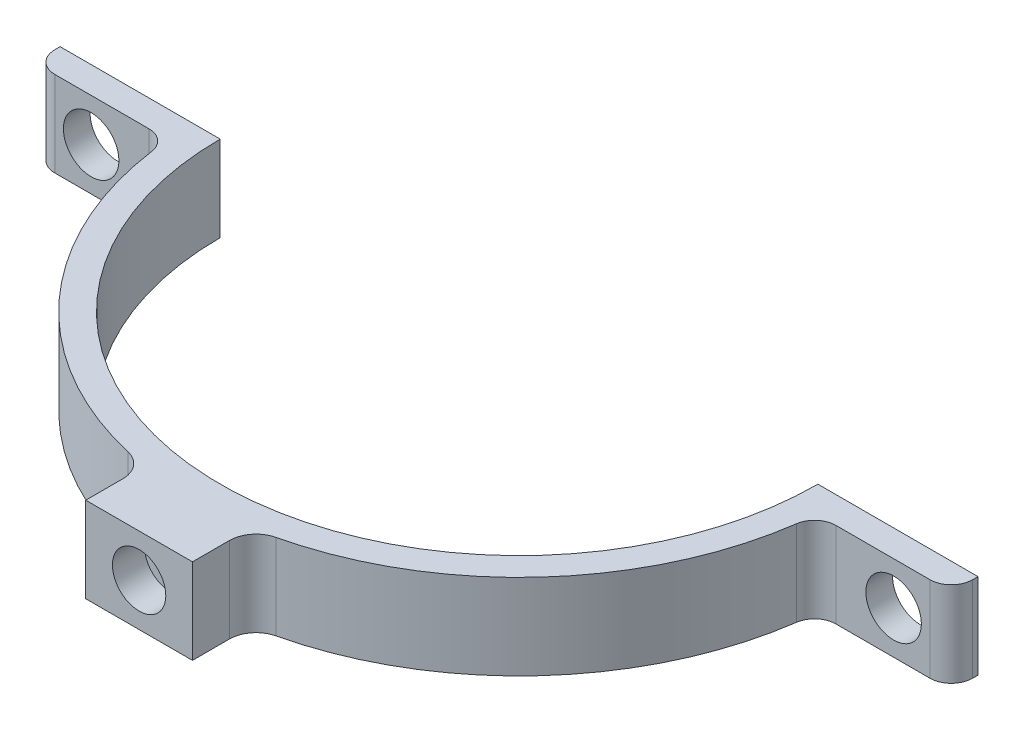
SolidWorks part; units mm, degrees
material "AISI 1020 Steel, Cold Rolled"
ref_plane "Front Plane" through (0, 0, 0) normal (0, 0, 1) x (1, 0, 0)
ref_plane "Top Plane" through (0, 0, 0) normal (0, 1, 0) x (1, 0, 0)
ref_plane "Right Plane" through (0, 0, 0) normal (1, 0, 0) x (0, 0, -1)
sketch "Sketch1" plane through (0, 0, 0) normal (0, 1, 0) x (1, 0, 0)
  line L0 (-54.61, 0) -> (54.61, 0) construction
  line L1 (-54.61, 0) -> (-54.61, -3.175)
  line L2 (-54.61, -3.175) -> (-38.6047, -3.175)
  line L3 (-54.61, 0) -> (-35.56, 0)
  line L4 (0, 0) -> (0, 11.898) construction
  line L5 (54.61, 0) -> (54.61, -3.175)
  line L6 (54.61, -3.175) -> (38.6047, -3.175)
  line L7 (54.61, 0) -> (35.56, 0)
  arc A0 (-35.56, 0) -> (35.56, 0) centre (0, 0) ccw
  arc A1 (-38.6047, -3.175) -> (38.6047, -3.175) centre (0, 0) ccw
  point P6 (0, 0)
  dimension "D1" = 71.12
  dimension "D2" = 3.175
  dimension "D3" = 3.175
  dimension "D4" = 19.05
extrude "Boss-Extrude1" add sketch "Sketch1" along normal blind 10.16
fillet "Fillet1" radius 2.54 2 edges at (38.6047, 5.08, 3.175) (-38.6047, 5.08, 3.175)
sketch "Sketch2" plane through (0, 0, 3.175) normal (0, 0, 1) x (1, 0, 0)
  line L0 (-47.7437, 10.16) -> (-47.7437, 0) construction
  line L1 (-54.61, 10.16) -> (-40.8774, 10.16) construction
  line L2 (-54.61, 0) -> (-40.8774, 0) construction
  line L3 (0, 0) -> (0, 20.3766) construction
  circle A0 centre (-47.7437, 5.08) radius 3.302
  circle A1 centre (47.7437, 5.08) radius 3.302
  dimension "D1" = 6.604
extrude "Cut-Extrude1" cut sketch "Sketch2" against normal blind 10.16
fillet "Fillet3" radius 2.54 2 edges at (-54.61, 5.08, 3.175) (54.61, 5.08, 3.175)
ref_plane "Plane2" through (0, 0, 38.735) normal (0, 0, 1) x (1, 0, 0)
sketch "Sketch4" plane through (0, 0, 38.735) normal (0, 0, 1) x (1, 0, 0)
  line L0 (-47.7437, 5.08) -> (47.7437, 5.08) construction
  line L1 (38.3619, 10.16) -> (-38.3619, 10.16) construction
  line L2 (-6.35, 0) -> (6.35, 0)
  line L3 (-6.35, 0) -> (-6.35, 10.16)
  line L4 (-6.35, 10.16) -> (6.35, 10.16)
  line L5 (6.35, 0) -> (6.35, 10.16)
  line L6 (-6.35, 0) -> (6.35, 10.16) construction
  line L7 (-6.35, 10.16) -> (6.35, 0) construction
  point P4 (0, 5.08)
  point P5 (0, 5.08)
  dimension "D1" = 12.7
extrude "Boss-Extrude2" add sketch "Sketch4" against normal up to surface up to face at (0, 5.08, 22.0492)
extrude "Boss-Extrude3" add sketch "Sketch4<2>" along normal blind 6.477
sketch "Sketch4<2>" plane through (0, 0, 38.735) normal (0, 0, 1) x (1, 0, 0) same geometry as "Sketch4"
fillet "Fillet4" radius 3.175 2 edges at (-6.35, 5.08, 38.211) (6.35, 5.08, 38.211)
sketch "Sketch5" plane through (0, 0, 45.212) normal (0, 0, 1) x (1, 0, 0)
  line L0 (0, 10.16) -> (0, 0) construction
  line L1 (6.35, 10.16) -> (-6.35, 10.16) construction
  line L2 (-6.35, 5.08) -> (6.35, 5.08) construction
  line L3 (-6.35, 10.16) -> (-6.35, 0) construction
  line L4 (6.35, 0) -> (6.35, 10.16) construction
  circle A0 centre (0, 5.08) radius 3.175
  point P11 (0, 5.08)
  dimension "D1" = 6.35
extrude "Cut-Extrude2" cut sketch "Sketch5" against normal blind 3.81
sketch "Sketch7" plane through (0, 0, 41.402) normal (0, 0, 1) x (1, 0, 0)
  circle A0 centre (0, 5.08) radius 1.905
  dimension "D1" = 3.81
extrude "Cut-Extrude3" cut sketch "Sketch7" against normal through all
cosmetic thread "Cosmetic Thread1" parameters "D2"=4.826
